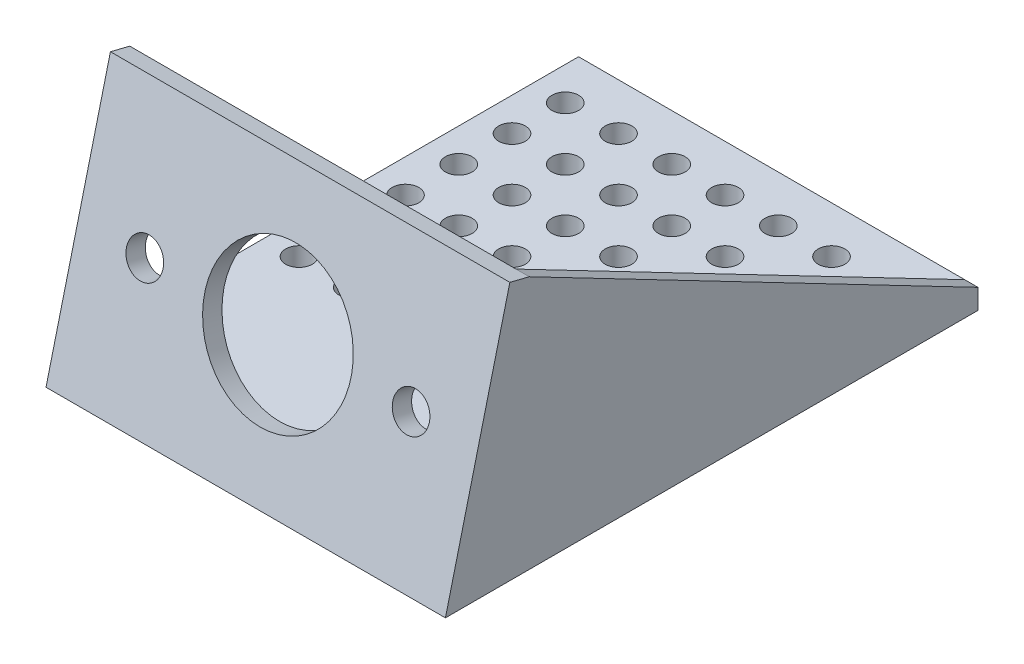
SolidWorks part; units mm, degrees
ref_plane "Front Plane" through (0, 0, 0) normal (0, 0, 1) x (1, 0, 0)
ref_plane "Top Plane" through (0, 0, 0) normal (0, 1, 0) x (1, 0, 0)
ref_plane "Right Plane" through (0, 0, 0) normal (1, 0, 0) x (0, 0, -1)
sketch "Sketch1" plane through (0, 0, 0) normal (1, 0, 0) x (0, 0, -1)
  line L0 (80, 0) -> (0, 0)
  line L1 (0, 0) -> (9.6769, 38.8118)
  line L2 (80, 3) -> (3.8398, 3)
  line L3 (3.8398, 3) -> (12.5878, 38.0861)
  line L4 (80, 0) -> (80, 3)
  line L5 (9.6769, 38.8118) -> (12.5878, 38.0861)
  line L6 (12.5878, 38.0861) -> (80, 3)
  dimension "D1" = 76
  dimension "D2" = 40
  dimension "D3" = 80
  dimension "D4" = 3
extrude "Boss-Extrude1" add sketch "Sketch1" against normal blind 2 contours L6 L3 L2 | L5 L1 L0 L4 L2 L3 region at (0, 0.8892, -40) region at (0, 14.6954, -32.1425)
extrude "Boss-Extrude2" add sketch "Sketch1<3>" against normal blind 60 contours L5 L1 L0 L4 L2 L3 region at (0, 0.8892, -40)
sketch "Sketch1<3>" plane through (0, 0, 0) normal (1, 0, 0) x (0, 0, -1) same geometry as "Sketch1"
sketch "Sketch2" plane through (0, 0, 0) normal (0, 0.2419, 0.9703) x (1, 0, 0)
  line L0 (-30, 40) -> (-30, 0) construction
  line L1 (-60, 40) -> (0, 40) construction
  line L2 (-60, 0) -> (0, 0) construction
  circle A0 centre (-30, 20) radius 11
  circle A1 centre (-50, 20) radius 2.75
  circle A2 centre (-10, 20) radius 2.75
  point P10 (0, 0)
  point P11 (-30, 20)
  point P12 (0, 0)
  dimension "D1" = 22
  dimension "D2" = 5.5
  dimension "D3" = 40
extrude "Cut-Extrude1" cut sketch "Sketch2" against normal up to next
sketch "Sketch3" plane through (0, 0, 0) normal (0, -1, 0) x (1, 0, 0)
  line L0 (-60, -80) -> (-60, 0) construction
  line L1 (-60, 0) -> (0, 0) construction
  circle A0 centre (-55, -33) radius 2
  circle A1 centre (-47, -33) radius 2
  circle A2 centre (-39, -33) radius 2
  circle A3 centre (-31, -33) radius 2
  circle A4 centre (-23, -33) radius 2
  circle A5 centre (-15, -33) radius 2
  circle A6 centre (-47, -41) radius 2
  circle A7 centre (-39, -41) radius 2
  circle A8 centre (-31, -41) radius 2
  circle A9 centre (-23, -41) radius 2
  circle A10 centre (-15, -41) radius 2
  circle A11 centre (-47, -49) radius 2
  circle A12 centre (-39, -49) radius 2
  circle A13 centre (-31, -49) radius 2
  circle A14 centre (-23, -49) radius 2
  circle A15 centre (-15, -49) radius 2
  circle A16 centre (-47, -57) radius 2
  circle A17 centre (-39, -57) radius 2
  circle A18 centre (-31, -57) radius 2
  circle A19 centre (-23, -57) radius 2
  circle A20 centre (-15, -57) radius 2
  circle A21 centre (-47, -65) radius 2
  circle A22 centre (-39, -65) radius 2
  circle A23 centre (-31, -65) radius 2
  circle A24 centre (-23, -65) radius 2
  circle A25 centre (-15, -65) radius 2
  circle A26 centre (-47, -73) radius 2
  circle A27 centre (-39, -73) radius 2
  circle A28 centre (-31, -73) radius 2
  circle A29 centre (-23, -73) radius 2
  circle A30 centre (-15, -73) radius 2
  circle A31 centre (-55, -41) radius 2
  circle A32 centre (-55, -49) radius 2
  circle A33 centre (-55, -57) radius 2
  circle A34 centre (-55, -65) radius 2
  circle A35 centre (-55, -73) radius 2
  dimension "D1" = 4
  dimension "D3" = 33
  dimension "D2" = 5
  dimension "D4" = 6
  dimension "D5" = 6
extrude "Cut-Extrude2" cut sketch "Sketch3" against normal up to next (3 mm away)
fillet "Fillet1" radius 4 1 edges at (-31, 3, -3.8398)
